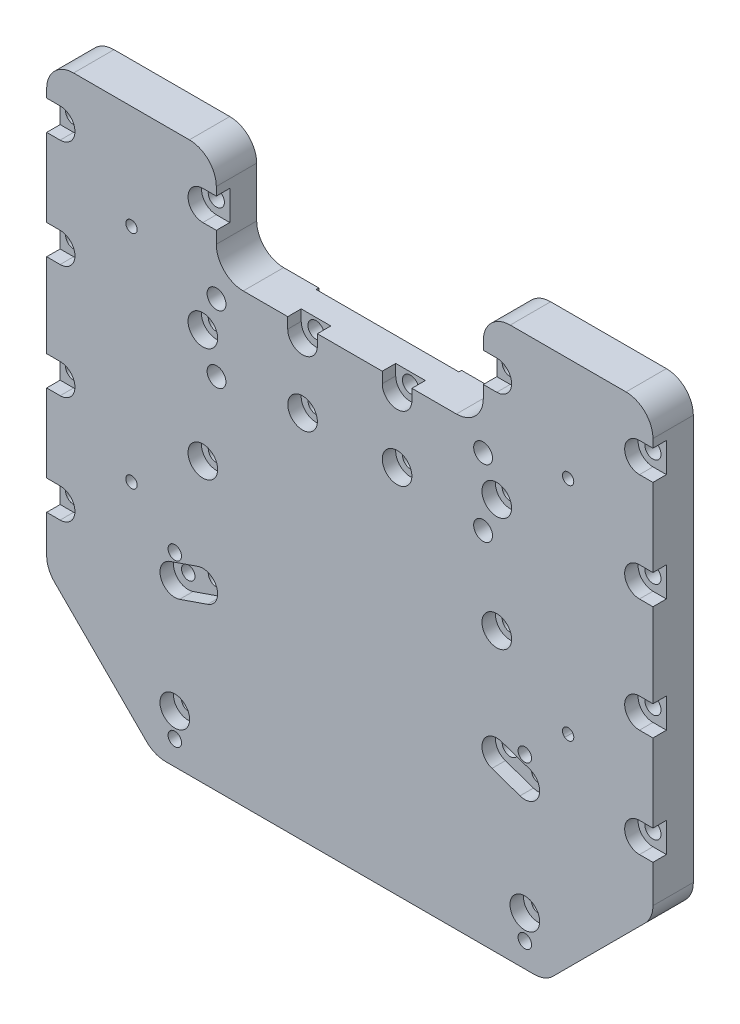
SolidWorks part; units mm, degrees
note: The reader was unsure of these and kept them because the rebuilt part matched: shared geometry of "Sketch16<3>", "Sketch16<4>".
ref_plane "Default Plane" through (193.6635, -121.6579, 15) normal (0, 0, -1) x (-1, 0, 0)
sketch3d "Bounding-Box_Cut-List-Item1"
  line L0 (225.1635, 160.2579, 0) -> (0, 160.2579, 0) construction
  line L1 (0, 160.2579, 0) -> (0, -44.1421, 0) construction
  line L2 (0, -44.1421, 0) -> (225.1635, -44.1421, 0) construction
  line L3 (225.1635, -44.1421, 0) -> (225.1635, 160.2579, 0) construction
  line L4 (225.1635, 160.2579, 15) -> (0, 160.2579, 15) construction
  line L5 (0, 160.2579, 15) -> (0, -44.1421, 15) construction
  line L6 (0, -44.1421, 15) -> (225.1635, -44.1421, 15) construction
  line L7 (225.1635, -44.1421, 15) -> (225.1635, 160.2579, 15) construction
  line L8 (225.1635, 160.2579, 0) -> (225.1635, 160.2579, 15) construction
  line L9 (0, 160.2579, 0) -> (0, 160.2579, 15) construction
  line L10 (0, -44.1421, 0) -> (0, -44.1421, 15) construction
  line L11 (225.1635, -44.1421, 0) -> (225.1635, -44.1421, 15) construction
material "6061 Alloy"
ref_plane "Front Plane" through (0, 0, 0) normal (0, 0, 1) x (1, 0, 0)
ref_plane "Top Plane" through (0, 0, 0) normal (0, 1, 0) x (1, 0, 0)
ref_plane "Right Plane" through (0, 0, 0) normal (1, 0, 0) x (0, 0, -1)
sketch "Sketch1" plane through (0, 0, 0) normal (0, 0, 1) x (1, 0, 0)
  line L0 (130.6635, -57.95) -> (130.6635, -106.45) construction
  line L1 (130.6635, -106.45) -> (131.6635, -107.45) construction
  line L2 (131.6635, -107.45) -> (140.6453, -107.45) construction
  line L3 (140.6453, -107.45) -> (140.6453, -120.8) construction
  line L4 (140.6453, -120.8) -> (183.6818, -120.8) construction
  line L5 (183.6818, -120.8) -> (183.6818, -107.45) construction
  line L6 (183.6818, -107.45) -> (192.6635, -107.45) construction
  line L7 (192.6635, -107.45) -> (193.6635, -106.45) construction
  line L8 (193.6635, -106.45) -> (193.6635, -57.95) construction
  line L9 (193.6635, -57.95) -> (192.6635, -56.95) construction
  line L10 (192.6635, -56.95) -> (183.6818, -56.95) construction
  line L11 (183.6818, -56.95) -> (183.6818, -43.6) construction
  line L12 (183.6818, -43.6) -> (140.6453, -43.6) construction
  line L13 (140.6453, -43.6) -> (140.6453, -56.95) construction
  line L14 (140.6453, -56.95) -> (131.6635, -56.95) construction
  line L15 (131.6635, -56.95) -> (130.6635, -57.95) construction
  line L16 (130.6635, 24.25) -> (130.6635, -24.25) construction
  line L17 (130.6635, -24.25) -> (131.6635, -25.25) construction
  line L18 (131.6635, -25.25) -> (140.6453, -25.25) construction
  line L19 (140.6453, -25.25) -> (140.6453, -38.6) construction
  line L20 (140.6453, -38.6) -> (183.6818, -38.6) construction
  line L21 (183.6818, -38.6) -> (183.6818, -25.25) construction
  line L22 (183.6818, -25.25) -> (192.6635, -25.25) construction
  line L23 (192.6635, -25.25) -> (193.6635, -24.25) construction
  line L24 (193.6635, -24.25) -> (193.6635, 24.25) construction
  line L25 (193.6635, 24.25) -> (192.6635, 25.25) construction
  line L26 (192.6635, 25.25) -> (183.6818, 25.25) construction
  line L27 (183.6818, 25.25) -> (183.6818, 38.6) construction
  line L28 (183.6818, 38.6) -> (140.6453, 38.6) construction
  line L29 (140.6453, 38.6) -> (140.6453, 25.25) construction
  line L30 (140.6453, 25.25) -> (131.6635, 25.25) construction
  line L31 (131.6635, 25.25) -> (130.6635, 24.25) construction
  line L32 (-31.5, -57.95) -> (-31.5, -106.45) construction
  line L33 (-31.5, -106.45) -> (-30.5, -107.45) construction
  line L34 (-30.5, -107.45) -> (-21.5182, -107.45) construction
  line L35 (-21.5182, -107.45) -> (-21.5182, -120.8) construction
  line L36 (-21.5182, -120.8) -> (21.5182, -120.8) construction
  line L37 (21.5182, -120.8) -> (21.5182, -107.45) construction
  line L38 (21.5182, -107.45) -> (30.5, -107.45) construction
  line L39 (30.5, -107.45) -> (31.5, -106.45) construction
  line L40 (31.5, -106.45) -> (31.5, -57.95) construction
  line L41 (31.5, -57.95) -> (30.5, -56.95) construction
  line L42 (30.5, -56.95) -> (21.5182, -56.95) construction
  line L43 (21.5182, -56.95) -> (21.5182, -43.6) construction
  line L44 (21.5182, -43.6) -> (-21.5182, -43.6) construction
  line L45 (-21.5182, -43.6) -> (-21.5182, -56.95) construction
  line L46 (-21.5182, -56.95) -> (-30.5, -56.95) construction
  line L47 (-30.5, -56.95) -> (-31.5, -57.95) construction
  line L48 (-31.5, 24.25) -> (-31.5, -24.25) construction
  line L49 (-31.5, -24.25) -> (-30.5, -25.25) construction
  line L50 (-30.5, -25.25) -> (-21.5182, -25.25) construction
  line L51 (-21.5182, -25.25) -> (-21.5182, -38.6) construction
  line L52 (-21.5182, -38.6) -> (21.5182, -38.6) construction
  line L53 (21.5182, -38.6) -> (21.5182, -25.25) construction
  line L54 (21.5182, -25.25) -> (30.5, -25.25) construction
  line L55 (30.5, -25.25) -> (31.5, -24.25) construction
  line L56 (31.5, -24.25) -> (31.5, 24.25) construction
  line L57 (31.5, 24.25) -> (30.5, 25.25) construction
  line L58 (30.5, 25.25) -> (21.5182, 25.25) construction
  line L59 (21.5182, 25.25) -> (21.5182, 38.6) construction
  line L60 (21.5182, 38.6) -> (-21.5182, 38.6) construction
  line L61 (-21.5182, 38.6) -> (-21.5182, 25.25) construction
  line L62 (-21.5182, 25.25) -> (-30.5, 25.25) construction
  line L63 (-30.5, 25.25) -> (-31.5, 24.25) construction
  line L64 (130.6635, -57.95) -> (130.6635, -106.45) construction
  line L65 (130.6635, -106.45) -> (131.6635, -107.45) construction
  line L66 (131.6635, -107.45) -> (140.6453, -107.45) construction
  line L67 (140.6453, -107.45) -> (140.6453, -120.8) construction
  line L68 (140.6453, -120.8) -> (183.6818, -120.8) construction
  line L69 (183.6818, -120.8) -> (183.6818, -107.45) construction
  line L70 (183.6818, -107.45) -> (192.6635, -107.45) construction
  line L71 (192.6635, -107.45) -> (193.6635, -106.45) construction
  line L72 (193.6635, -106.45) -> (193.6635, -57.95) construction
  line L73 (193.6635, -57.95) -> (192.6635, -56.95) construction
  line L74 (192.6635, -56.95) -> (183.6818, -56.95) construction
  line L75 (183.6818, -56.95) -> (183.6818, -43.6) construction
  line L76 (183.6818, -43.6) -> (140.6453, -43.6) construction
  line L77 (140.6453, -43.6) -> (140.6453, -56.95) construction
  line L78 (140.6453, -56.95) -> (131.6635, -56.95) construction
  line L79 (131.6635, -56.95) -> (130.6635, -57.95) construction
  line L80 (130.6635, 24.25) -> (130.6635, -24.25) construction
  line L81 (130.6635, -24.25) -> (131.6635, -25.25) construction
  line L82 (131.6635, -25.25) -> (140.6453, -25.25) construction
  line L83 (140.6453, -25.25) -> (140.6453, -38.6) construction
  line L84 (140.6453, -38.6) -> (183.6818, -38.6) construction
  line L85 (183.6818, -38.6) -> (183.6818, -25.25) construction
  line L86 (183.6818, -25.25) -> (192.6635, -25.25) construction
  line L87 (192.6635, -25.25) -> (193.6635, -24.25) construction
  line L88 (193.6635, -24.25) -> (193.6635, 24.25) construction
  line L89 (193.6635, 24.25) -> (192.6635, 25.25) construction
  line L90 (192.6635, 25.25) -> (183.6818, 25.25) construction
  line L91 (183.6818, 25.25) -> (183.6818, 38.6) construction
  line L92 (183.6818, 38.6) -> (140.6453, 38.6) construction
  line L93 (140.6453, 38.6) -> (140.6453, 25.25) construction
  line L94 (140.6453, 25.25) -> (131.6635, 25.25) construction
  line L95 (131.6635, 25.25) -> (130.6635, 24.25) construction
  line L96 (-31.5, -57.95) -> (-31.5, -106.45) construction
  line L97 (-31.5, -106.45) -> (-30.5, -107.45) construction
  line L98 (-30.5, -107.45) -> (-21.5182, -107.45) construction
  line L99 (-21.5182, -107.45) -> (-21.5182, -120.8) construction
  line L100 (-21.5182, -120.8) -> (21.5182, -120.8) construction
  line L101 (21.5182, -120.8) -> (21.5182, -107.45) construction
  line L102 (21.5182, -107.45) -> (30.5, -107.45) construction
  line L103 (30.5, -107.45) -> (31.5, -106.45) construction
  line L104 (31.5, -106.45) -> (31.5, -57.95) construction
  line L105 (31.5, -57.95) -> (30.5, -56.95) construction
  line L106 (30.5, -56.95) -> (21.5182, -56.95) construction
  line L107 (21.5182, -56.95) -> (21.5182, -43.6) construction
  line L108 (21.5182, -43.6) -> (-21.5182, -43.6) construction
  line L109 (-21.5182, -43.6) -> (-21.5182, -56.95) construction
  line L110 (-21.5182, -56.95) -> (-30.5, -56.95) construction
  line L111 (-30.5, -56.95) -> (-31.5, -57.95) construction
  line L112 (-31.5, 24.25) -> (-31.5, -24.25) construction
  line L113 (-31.5, -24.25) -> (-30.5, -25.25) construction
  line L114 (-30.5, -25.25) -> (-21.5182, -25.25) construction
  line L115 (-21.5182, -25.25) -> (-21.5182, -38.6) construction
  line L116 (-21.5182, -38.6) -> (21.5182, -38.6) construction
  line L117 (21.5182, -38.6) -> (21.5182, -25.25) construction
  line L118 (21.5182, -25.25) -> (30.5, -25.25) construction
  line L119 (30.5, -25.25) -> (31.5, -24.25) construction
  line L120 (31.5, -24.25) -> (31.5, 24.25) construction
  line L121 (31.5, 24.25) -> (30.5, 25.25) construction
  line L122 (30.5, 25.25) -> (21.5182, 25.25) construction
  line L123 (21.5182, 25.25) -> (21.5182, 38.6) construction
  line L124 (21.5182, 38.6) -> (-21.5182, 38.6) construction
  line L125 (-21.5182, 38.6) -> (-21.5182, 25.25) construction
  line L126 (-21.5182, 25.25) -> (-30.5, 25.25) construction
  line L127 (-30.5, 25.25) -> (-31.5, 24.25) construction
  line L129 (-31.5, 38.6) -> (193.6635, 38.6)
  line L130 (-31.5, 38.6) -> (-31.5, -165.8)
  line L131 (-31.5, -165.8) -> (193.6635, -165.8)
  line L132 (193.6635, 38.6) -> (193.6635, -165.8)
  circle A1 centre (188.6635, -102.2) radius 2.5
  circle A2 centre (188.6635, -102.2) radius 2.5 construction
  circle A3 centre (188.6635, -62.2) radius 2.5
  circle A4 centre (188.6635, -62.2) radius 2.5 construction
  circle A5 centre (135.6635, -62.2) radius 2.5
  circle A6 centre (135.6635, -62.2) radius 2.5 construction
  circle A7 centre (135.6635, -102.2) radius 2.5
  circle A8 centre (135.6635, -102.2) radius 2.5 construction
  circle A9 centre (188.6635, -20) radius 2.5
  circle A10 centre (188.6635, -20) radius 2.5 construction
  circle A11 centre (188.6635, 20) radius 2.5
  circle A12 centre (188.6635, 20) radius 2.5 construction
  circle A13 centre (135.6635, 20) radius 2.5
  circle A14 centre (135.6635, 20) radius 2.5 construction
  circle A15 centre (135.6635, -20) radius 2.5
  circle A16 centre (135.6635, -20) radius 2.5 construction
  circle A17 centre (26.5, -102.2) radius 2.5
  circle A18 centre (26.5, -102.2) radius 2.5 construction
  circle A19 centre (26.5, -62.2) radius 2.5
  circle A20 centre (26.5, -62.2) radius 2.5 construction
  circle A21 centre (-26.5, -62.2) radius 2.5
  circle A22 centre (-26.5, -62.2) radius 2.5 construction
  circle A23 centre (-26.5, -102.2) radius 2.5
  circle A24 centre (-26.5, -102.2) radius 2.5 construction
  circle A25 centre (26.5, -20) radius 2.5
  circle A26 centre (26.5, -20) radius 2.5 construction
  circle A27 centre (26.5, 20) radius 2.5
  circle A28 centre (26.5, 20) radius 2.5 construction
  circle A29 centre (-26.5, 20) radius 2.5
  circle A30 centre (-26.5, 20) radius 2.5 construction
  circle A31 centre (-26.5, -20) radius 2.5
  circle A32 centre (-26.5, -20) radius 2.5 construction
  circle A33 centre (63.5318, -28.2202) radius 2.15
  circle A34 centre (63.5318, -28.2202) radius 2.15
  circle A35 centre (98.6318, -28.2202) radius 2.15
  circle A36 centre (98.6318, -28.2202) radius 2.15
  circle A37 centre (98.6318, -4.0202) radius 2.15
  circle A38 centre (98.6318, -4.0202) radius 2.15
  circle A39 centre (63.5318, -4.0202) radius 2.15
  circle A40 centre (63.5318, -4.0202) radius 2.15
  dimension "D17" = 45
  dimension "D1" = 0
  dimension "D2" = 0
  dimension "D3" = 0
  dimension "D4" = 0
  dimension "D5" = 0
  dimension "D6" = 0
  dimension "D7" = 0
  dimension "D8" = 0
  dimension "D9" = 0
  dimension "D10" = 0
  dimension "D11" = 0
  dimension "D12" = 0
  dimension "D13" = 0
  dimension "D14" = 0
  dimension "D15" = 0
  dimension "D16" = 0
  dimension "D18" = 0
  dimension "D19" = 0
  dimension "D20" = 0
  dimension "D21" = 0
extrude "Boss-Extrude1" add sketch "Sketch1" along normal blind 15 contours L129 L132 L131 L130
sketch "holesLocations" plane through (0, 0, 15) normal (0, 0, 1) x (1, 0, 0)
  line L0 (135.6635, 20) -> (188.6635, -20) construction
  line L1 (135.6635, -62.2) -> (188.6635, -102.2) construction
  line L2 (-26.5, 20) -> (26.5, -20) construction
  line L3 (-26.5, -62.2) -> (26.5, -102.2) construction
  circle A0 centre (63.5318, -28.2202) radius 2.15 construction
  circle A1 centre (98.6318, -28.2202) radius 2.15 construction
  circle A2 centre (98.6318, -4.0202) radius 2.15 construction
  circle A3 centre (63.5318, -4.0202) radius 2.15 construction
  circle A4 centre (63.5318, -28.2202) radius 2.15
  circle A5 centre (98.6318, -28.2202) radius 2.15
  circle A6 centre (98.6318, -4.0202) radius 2.15
  circle A7 centre (63.5318, -4.0202) radius 2.15
  point P0 (135.6635, -20)
  point P2 (135.6635, 20)
  point P4 (188.6635, 20)
  point P6 (188.6635, -20)
  point P8 (188.6635, -62.2)
  point P10 (135.6635, -62.2)
  point P12 (188.6635, -102.2)
  point P14 (135.6635, -102.2)
  point P16 (-26.5, -102.2)
  point P18 (26.5, -62.2)
  point P20 (26.5, -102.2)
  point P22 (-26.5, -62.2)
  point P24 (-26.5, -20)
  point P26 (26.5, -20)
  point P28 (26.5, 20)
  point P30 (-26.5, 20)
  point P40 (0, 0)
  point P41 (0, -82.2)
  point P43 (162.1635, -82.2)
  point P44 (162.1635, 0)
hole_wizard "Hole1" positions "3DSketch1" profile "Sketch5" legacy end condition up to next
sketch3d "3DSketch1"
  point P0 (-26.5, 20, 15)
  point P3 (26.5, -20, 15)
  point P6 (26.5, 20, 15)
  point P9 (-26.5, -20, 15)
  point P12 (26.5, -62.2, 15)
  point P15 (26.5, -102.2, 15)
  point P18 (-26.5, -62.2, 15)
  point P21 (-26.5, -102.2, 15)
  point P24 (135.6635, 20, 15)
  point P27 (135.6635, -20, 15)
  point P30 (188.6635, 20, 15)
  point P33 (188.6635, -62.2, 15)
  point P36 (188.6635, -20, 15)
  point P39 (135.6635, -102.2, 15)
  point P42 (135.6635, -62.2, 15)
  point P45 (188.6635, -102.2, 15)
  point P48 (63.5318, -4.0202, 15)
  point P51 (63.5318, -28.2202, 15)
  point P54 (98.6318, -28.2202, 15)
  point P57 (98.6318, -4.0202, 15)
sketch "Sketch5" plane through (-26.5, 20, 15) normal (1, 0, 0) x (0, -1, 0)
  line L0 (0, 0) -> (0, 15)
  line L1 (0, 15) -> (3, 15)
  line L2 (3, 15) -> (3, 5)
  line L3 (3, 5) -> (5.5, 5)
  line L4 (5.5, 5) -> (5.5, 0)
  line L5 (5.5, 0) -> (0, 0)
  line L6 (0, 110) -> (0, -10) construction
  dimension "Diameter" = 6
  dimension "Depth" = 15
  dimension "C-Bore Diameter" = 11
  dimension "C-Bore Depth" = 5
hole_wizard "M5x0.8 Tapped Hole1" positions "3DSketch2" profile "Sketch7" tap size "M5x0.8" standard "ANSI Metric" end condition up to next
sketch3d "3DSketch2"
  line L0 (135.6635, -62.2, 15) -> (188.6635, -102.2, 15) construction
  line L1 (-26.5, 20, 15) -> (26.5, -20, 15) construction
  point P0 (0, 0, 0)
  point P3 (0, -82.2, 15)
  point P6 (162.1635, 0, 15)
  point P13 (162.1635, -82.2, 15)
  point P15 (162.1635, -82.2, 15)
  point P17 (162.1635, -82.2, 15)
  point P19 (0, 0, 15)
  point P30 (162.1635, -82.2, 15)
  point P32 (162.164, -82.2004, 15)
sketch "Sketch7" plane through (162.164, -82.2004, 15) normal (1, 0, 0) x (0, -1, 0)
  line L0 (0, 0) -> (0, 15.001)
  line L1 (0, 15.001) -> (2.1, 15.001)
  line L2 (2.1, 15.001) -> (2.1, 0)
  line L5 (2.1, 0) -> (0, 0)
  line L11 (0, -6.35) -> (0, 107.95) construction
  dimension "Thru Tap Drill Dia." = 4.2
  dimension "Thru Tap Drill Depth" = 15.001
cosmetic thread "Hole Thread9" parameters "D2"=5
cosmetic thread "Hole Thread11" parameters "D2"=5
cosmetic thread "Hole Thread14" parameters "D2"=5
cosmetic thread "Hole Thread15" parameters "D2"=5
cosmetic thread "Hole Thread16" parameters "D2"=5
cosmetic thread "Hole Thread17" parameters "D2"=5
sketch "Sketch9" plane through (0, 0, 15) normal (0, 0, 1) x (1, 0, 0)
  line L0 (-31.5, 38.6) -> (-31.5, 22.2913) construction
  line L1 (-26.5, 14.5) -> (-31.5, 14.5)
  line L2 (-26.5, 14.5) -> (-26.5, 25.5)
  line L3 (-26.5, 25.5) -> (-31.5, 25.5)
  line L4 (-31.5, 14.5) -> (-31.5, 25.5)
  line L5 (-31.5, 17.7087) -> (-31.5, -17.7087) construction
  line L6 (-26.5, -25.5) -> (-31.5, -25.5)
  line L7 (-26.5, -25.5) -> (-26.5, -14.5)
  line L8 (-26.5, -14.5) -> (-31.5, -14.5)
  line L9 (-31.5, -25.5) -> (-31.5, -14.5)
  line L10 (-31.5, -22.2913) -> (-31.5, -59.9087) construction
  line L11 (-26.5, -67.7) -> (-31.5, -67.7)
  line L12 (-26.5, -67.7) -> (-26.5, -56.7)
  line L13 (-26.5, -56.7) -> (-31.5, -56.7)
  line L14 (-31.5, -67.7) -> (-31.5, -56.7)
  line L15 (-31.5, -64.4913) -> (-31.5, -99.9087) construction
  line L16 (-26.5, -107.7) -> (-31.5, -107.7)
  line L17 (-26.5, -107.7) -> (-26.5, -96.7)
  line L18 (-26.5, -96.7) -> (-31.5, -96.7)
  line L19 (-31.5, -107.7) -> (-31.5, -96.7)
  line L20 (193.6635, 17.7087) -> (193.6635, -17.7087) construction
  line L21 (188.6635, 25.5) -> (193.6635, 25.5)
  line L22 (188.6635, 25.5) -> (188.6635, 14.5)
  line L23 (188.6635, 14.5) -> (193.6635, 14.5)
  line L24 (193.6635, 25.5) -> (193.6635, 14.5)
  line L25 (193.6635, -22.2913) -> (193.6635, -59.9087) construction
  line L26 (188.6635, -14.5) -> (193.6635, -14.5)
  line L27 (188.6635, -14.5) -> (188.6635, -25.5)
  line L28 (188.6635, -25.5) -> (193.6635, -25.5)
  line L29 (193.6635, -14.5) -> (193.6635, -25.5)
  line L30 (193.6635, -64.4913) -> (193.6635, -99.9087) construction
  line L31 (188.6635, -56.7) -> (193.6635, -56.7)
  line L32 (188.6635, -56.7) -> (188.6635, -67.7)
  line L33 (188.6635, -67.7) -> (193.6635, -67.7)
  line L34 (193.6635, -56.7) -> (193.6635, -67.7)
  line L35 (193.6635, -104.4913) -> (193.6635, -165.8) construction
  line L36 (188.6635, -96.7) -> (193.6635, -96.7)
  line L37 (188.6635, -96.7) -> (188.6635, -107.7)
  line L38 (188.6635, -107.7) -> (193.6635, -107.7)
  line L39 (193.6635, -96.7) -> (193.6635, -107.7)
  arc A0 (-31.5, 17.7087) -> (-31.5, 22.2913) centre (-26.5, 20) ccw construction
  arc A1 (-31.5, -22.2913) -> (-31.5, -17.7087) centre (-26.5, -20) ccw construction
  arc A2 (-31.5, -64.4913) -> (-31.5, -59.9087) centre (-26.5, -62.2) ccw construction
  arc A3 (-31.5, -104.4913) -> (-31.5, -99.9087) centre (-26.5, -102.2) ccw construction
  arc A4 (193.6635, 22.2913) -> (193.6635, 17.7087) centre (188.6635, 20) ccw construction
  arc A5 (193.6635, -17.7087) -> (193.6635, -22.2913) centre (188.6635, -20) ccw construction
  arc A6 (193.6635, -59.9087) -> (193.6635, -64.4913) centre (188.6635, -62.2) ccw construction
  arc A7 (193.6635, -99.9087) -> (193.6635, -104.4913) centre (188.6635, -102.2) ccw construction
  arc M23 (-31.5, 22.2913) -> (-31.5, 17.7087) centre (-26.5, 20) cw
  line M24 (-31.5, 17.7087) -> (-31.5, -17.7087)
  arc M25 (-31.5, -17.7087) -> (-31.5, -22.2913) centre (-26.5, -20) cw
  line M26 (-31.5, -22.2913) -> (-31.5, -59.9087)
  arc M27 (-31.5, -59.9087) -> (-31.5, -64.4913) centre (-26.5, -62.2) cw
  line M28 (-31.5, -64.4913) -> (-31.5, -99.9087)
  arc M29 (-31.5, -99.9087) -> (-31.5, -104.4913) centre (-26.5, -102.2) cw
  line M30 (-31.5, -104.4913) -> (-31.5, -165.8)
  line M32 (193.6635, -165.8) -> (193.6635, -104.4913)
  arc M33 (193.6635, -104.4913) -> (193.6635, -99.9087) centre (188.6635, -102.2) cw
  line M34 (193.6635, -99.9087) -> (193.6635, -64.4913)
  arc M35 (193.6635, -64.4913) -> (193.6635, -59.9087) centre (188.6635, -62.2) cw
  line M36 (193.6635, -59.9087) -> (193.6635, -22.2913)
  arc M37 (193.6635, -22.2913) -> (193.6635, -17.7087) centre (188.6635, -20) cw
  line M38 (193.6635, -17.7087) -> (193.6635, 17.7087)
  arc M39 (193.6635, 17.7087) -> (193.6635, 22.2913) centre (188.6635, 20) cw
  line M40 (193.6635, 22.2913) -> (193.6635, 38.6)
  line M42 (-31.5, 38.6) -> (-31.5, 22.2913)
extrude "Cut-Extrude1" cut sketch "Sketch9" against normal up to surface (5 mm away) contours L1 M23 M24 | L3 M23 M42 | L8 M25 M24 | L6 M25 M26 | L13 M27 M26 | L11 M27 M28 | L18 M29 M28 | L16 M29 M30 | L38 M33 M32 | L36 M33 M34 | L33 M35 M34 | L31 M35 M36 | L28 M37 M36 | L26 M37 M38 | L23 M39 M38 | L21 M39 M40 up to face at (-23.5, 20, 10)
sketch "Sketch10" plane through (0, 0, 15) normal (0, 0, 1) x (1, 0, 0)
  line L0 (-31.5, -165.8) -> (193.6635, -165.8) construction
  line L1 (16.0818, -156.8) -> (146.0818, -156.8)
  line L2 (16.0818, -156.8) -> (16.0818, -96.8)
  line L3 (16.0818, -96.8) -> (146.0818, -96.8)
  line L4 (146.0818, -156.8) -> (146.0818, -96.8)
  line L5 (16.0818, -147.8) -> (146.0818, -147.8)
  line L6 (16.0818, -147.8) -> (16.0818, -105.8)
  line L7 (16.0818, -105.8) -> (146.0818, -105.8)
  line L8 (146.0818, -147.8) -> (146.0818, -105.8)
  line L9 (81.0818, -156.8) -> (81.0818, -165.8)
  dimension "D1" = 130
  dimension "D2" = 60
  dimension "D3" = 42
  dimension "D4" = 9
  dimension "D5" = 18
hole_wizard "M6x1.0 Tapped Hole1" positions "3DSketch3" profile "Sketch12" tap size "M6x1.0" standard "ANSI Metric" end condition up to next
sketch3d "3DSketch3"
  point P0 (16.0818, -96.8, 15)
  point P3 (146.0818, -96.8, 15)
  point P6 (146.0818, -156.8, 15)
  point P9 (16.0818, -156.8, 15)
sketch "Sketch12" plane through (16.0818, -96.8, 15) normal (1, 0, 0) x (0, -1, 0)
  line L0 (0, 0) -> (0, 15)
  line L1 (0, 15) -> (2.5, 15)
  line L2 (2.5, 15) -> (2.5, 0)
  line L5 (2.5, 0) -> (0, 0)
  line L11 (0, -6.35) -> (0, 107.95) construction
  dimension "Thru Tap Drill Dia." = 5
  dimension "Thru Tap Drill Depth" = 15
cosmetic thread "Hole Thread5" parameters "D2"=6
cosmetic thread "Hole Thread6" parameters "D2"=6
cosmetic thread "Hole Thread7" parameters "D2"=6
cosmetic thread "Hole Thread8" parameters "D2"=6
hole_wizard "Hole2" positions "3DSketch4" profile "Sketch14" legacy end condition up to next
sketch3d "3DSketch4"
  point P0 (16.0818, -105.8, 15)
  point P3 (16.0818, -147.8, 15)
  point P6 (146.0818, -105.8, 15)
  point P9 (146.0818, -147.8, 15)
sketch "Sketch14" plane through (16.0818, -105.8, 15) normal (1, 0, 0) x (0, -1, 0)
  line L0 (0, 0) -> (0, 15)
  line L1 (0, 15) -> (2.5, 15)
  line L2 (2.5, 15) -> (2.5, 5)
  line L3 (2.5, 5) -> (5.5, 5)
  line L4 (5.5, 5) -> (5.5, 0)
  line L5 (5.5, 0) -> (0, 0)
  line L6 (0, 110) -> (0, -10) construction
  dimension "Diameter" = 5
  dimension "Depth" = 15
  dimension "C-Bore Diameter" = 11
  dimension "C-Bore Depth" = 5
sketch "Sketch15" plane through (0, 0, 15) normal (0, 0, 1) x (1, 0, 0)
  line L0 (14.2855, -100.6016) -> (24.7037, -97.0016)
  line L1 (17.8781, -110.9984) -> (28.2963, -107.3984)
  line L2 (81.0818, 38.6) -> (81.0818, -165.8) construction
  line L3 (-31.5, 38.6) -> (193.6635, 38.6) construction
  line L4 (-31.5, -165.8) -> (193.6635, -165.8) construction
  line L5 (144.2855, -110.9984) -> (133.8672, -107.3984)
  line L6 (147.8781, -100.6016) -> (137.4598, -97.0016)
  circle A0 centre (26.5, -102.2) radius 5.5 construction
  circle A1 centre (16.0818, -105.8) radius 5.5 construction
  circle A2 centre (26.5, -102.2) radius 5.5 construction
  circle A3 centre (26.5, -102.2) radius 5.5
  circle A4 centre (16.0818, -105.8) radius 5.5
  circle A5 centre (146.0818, -105.8) radius 5.5
  circle A6 centre (135.6635, -102.2) radius 5.5
extrude "Cut-Extrude2" cut sketch "Sketch15" against normal up to surface (5 mm away) contours A4 L1 A3 L0 | L6 A6 L5 A5 up to face at (138.6635, -102.2, 10)
chamfer "Chamfer1" distance 40 angle 45 2 edges at (193.6635, -165.8, 7.5) (-31.5, -165.8, 7.5)
sketch "Sketch16" plane through (0, 0, 0) normal (0, 0, -1) x (-1, 0, 0)
  line L0 (-73.2681, 13.4798) -> (-66.2681, 13.4798) construction
  line L1 (-73.2681, 13.4798) -> (-66.2681, 13.4798)
  line L2 (-105.5818, 1.3798) -> (-105.5818, -33.6202) construction
  line L3 (-105.5818, -33.6202) -> (-56.5818, -33.6202) construction
  line L4 (-56.5818, -33.6202) -> (-56.5818, 1.3798) construction
  line L5 (-56.5818, 1.3798) -> (-105.5818, 1.3798) construction
  line L6 (-95.7787, 1.8798) -> (-66.3848, 1.8798) construction
  line L7 (-66.3848, 1.8798) -> (-66.3848, 9.8798) construction
  line L8 (-66.3848, 9.8798) -> (-95.7787, 9.8798) construction
  line L9 (-95.7787, 9.8798) -> (-95.7787, 1.8798) construction
  line L10 (-75.0818, 9.8798) -> (-87.0818, 9.8798) construction
  line L11 (-105.5818, 1.3798) -> (-105.5818, -33.6202)
  line L12 (-105.5818, -33.6202) -> (-56.5818, -33.6202)
  line L13 (-56.5818, -33.6202) -> (-56.5818, 1.3798)
  line L14 (-56.5818, 1.3798) -> (-105.5818, 1.3798)
  line L15 (-95.7787, 1.8798) -> (-66.3848, 1.8798)
  line L16 (-66.3848, 1.8798) -> (-66.3848, 9.8798)
  line L17 (-66.3848, 9.8798) -> (-95.7787, 9.8798)
  line L18 (-95.7787, 9.8798) -> (-95.7787, 1.8798)
  line L19 (-75.0818, 9.8798) -> (-87.0818, 9.8798)
  line L20 (31.5, 38.6) -> (-193.6635, 38.6) construction
  line L21 (-107.5818, -35.6202) -> (-54.5818, -35.6202)
  line L22 (-107.5818, -35.6202) -> (-107.5818, 38.6)
  line L23 (-107.5818, 38.6) -> (-54.5818, 38.6)
  line L24 (-54.5818, -35.6202) -> (-54.5818, 38.6)
  line L25 (-8.5, -165.8) -> (-153.6635, -165.8) construction
  line L26 (-107.5818, 38.6) -> (-54.5818, 38.6)
  line L27 (-107.5818, 38.6) -> (-107.5818, 1.4899)
  line L28 (-107.5818, 1.4899) -> (-54.5818, 1.4899)
  line L29 (-54.5818, 38.6) -> (-54.5818, 1.4899)
  line L30 (-107.5818, -35.6202) -> (-54.5818, -35.6202)
  line L31 (-107.5818, -35.6202) -> (-107.5818, -165.8)
  line L32 (-107.5818, -165.8) -> (-54.5818, -165.8)
  line L33 (-54.5818, -35.6202) -> (-54.5818, -165.8)
  line L34 (-130.6635, 24.25) -> (-130.6635, -24.25) construction
  line L35 (-130.6635, 0) -> (-31.5, 0)
  line L36 (-130.6635, 0) -> (-130.6635, 38.6)
  line L37 (-130.6635, 38.6) -> (-31.5, 38.6)
  line L38 (-31.5, 0) -> (-31.5, 38.6)
  line L39 (-31.5, -24.25) -> (-31.5, 24.25) construction
  line L40 (-130.6635, 24.25) -> (-130.6635, -24.25)
  line L41 (-31.5, -24.25) -> (-31.5, 24.25)
  line M42 (-153.6635, -165.8) -> (-8.5, -165.8)
  dimension "D1" = 2
  dimension "D2" = 2
  dimension "D3" = 2
extrude "Cut-Extrude3" cut sketch "Sketch16" against normal blind 1
extrude "Cut-Extrude4" cut sketch "Sketch16<3>" against normal offset from surface (5 mm away) 2 contours L33 L21 L31 M42 offset beyond the face yes
sketch "Sketch16<3>" plane through (0, 0, 0) normal (0, 0, -1) x (-1, 0, 0) same geometry as "Sketch16"
extrude "Cut-Extrude5" cut sketch "Sketch16<4>" against normal through all
sketch "Sketch16<4>" plane through (0, 0, 0) normal (0, 0, -1) x (-1, 0, 0) same geometry as "Sketch16"
sketch "Sketch17" plane through (0, 0, 15) normal (0, 0, 1) x (1, 0, 0)
  line L0 (26.5, 20) -> (37.5353, 20) construction
  line L1 (26.5, 25.5) -> (37.5353, 25.5)
  line L2 (26.5, 14.5) -> (37.5353, 14.5)
  line L3 (63.5318, -4.0202) -> (63.5318, 6.879) construction
  line L4 (58.0318, -4.0202) -> (58.0318, 6.879)
  line L5 (69.0318, -4.0202) -> (69.0318, 6.879)
  line L6 (98.6318, -4.0202) -> (98.6318, 8.2381) construction
  line L7 (93.1318, -4.0202) -> (93.1318, 8.2381)
  line L8 (104.1318, -4.0202) -> (104.1318, 8.2381)
  line L9 (135.6635, 20) -> (124.6727, 20) construction
  line L10 (135.6635, 14.5) -> (124.6727, 14.5)
  line L11 (135.6635, 25.5) -> (124.6727, 25.5)
  arc A0 (26.5, 25.5) -> (26.5, 14.5) centre (26.5, 20) ccw
  arc A1 (37.5353, 14.5) -> (37.5353, 25.5) centre (37.5353, 20) ccw
  arc A2 (58.0318, -4.0202) -> (69.0318, -4.0202) centre (63.5318, -4.0202) ccw
  arc A3 (69.0318, 6.879) -> (58.0318, 6.879) centre (63.5318, 6.879) ccw
  arc A4 (93.1318, -4.0202) -> (104.1318, -4.0202) centre (98.6318, -4.0202) ccw
  arc A5 (104.1318, 8.2381) -> (93.1318, 8.2381) centre (98.6318, 8.2381) ccw
  arc A6 (135.6635, 14.5) -> (135.6635, 25.5) centre (135.6635, 20) ccw
  arc A7 (124.6727, 25.5) -> (124.6727, 14.5) centre (124.6727, 20) ccw
  arc A8 (31.5, 22.2913) -> (31.5, 17.7087) centre (26.5, 20) ccw construction
  arc A9 (59.7783, 0) -> (67.2852, 0) centre (63.5318, -4.0202) ccw construction
  arc A10 (94.8783, 0) -> (102.3852, 0) centre (98.6318, -4.0202) ccw construction
  arc A11 (130.6635, 17.7087) -> (130.6635, 22.2913) centre (135.6635, 20) ccw construction
  point P3 (32.0176, 20)
  point P8 (63.5318, 1.4294)
  point P16 (98.6318, 2.109)
  point P24 (130.1681, 20)
extrude "Cut-Extrude6" cut sketch "Sketch17" against normal up to surface (5 mm away) up to face at (66.5318, -4.0202, 10)
fillet "Fillet1" radius 10 10 edges at (-31.5, -125.8, 7.5) (8.5, -165.8, 7.5) (153.6635, -165.8, 7.5) (193.6635, -125.8, 7.5) (193.6635, 38.6, 7.5) (130.6635, 38.6, 7.5) (130.6635, 0, 7.5) (31.5, 0, 7.5) (-31.5, 38.6, 7.5) (31.5, 38.6, 7.5)
sketch "Sketch18" plane through (0, 0, 15) normal (0, 0, 1) x (1, 0, 0)
  line L0 (26.5, -20) -> (31.5818, -20) construction
  line L1 (81.0818, 0) -> (81.0818, -63.4482) construction
  line L2 (31.5818, -7.5) -> (130.5818, -7.5) construction
  line L3 (31.5818, -7.5) -> (31.5818, -32.5) construction
  line L4 (31.5818, -32.5) -> (130.5818, -32.5) construction
  line L5 (130.5818, -7.5) -> (130.5818, -32.5) construction
  line L7 (69.0318, 0) -> (93.1318, 0) construction
  point P8 (81.0818, -7.5)
  point P15 (31.5818, -20)
  dimension "D1" = 99
  dimension "D2" = 25
hole_wizard "oldSpindleMountM8holes" positions "3DSketch5" profile "Sketch19" tap size "M8x1.0" standard "ANSI Metric" end condition through all
sketch3d "3DSketch5"
  point P0 (31.5818, -7.5, 15)
  point P3 (31.5818, -32.5, 15)
  point P6 (130.5818, -7.5, 15)
  point P9 (130.5818, -32.5, 15)
sketch "Sketch19" plane through (31.5818, -7.5, 15) normal (1, 0, 0) x (0, -1, 0)
  line L0 (0, 0) -> (0, 15.005)
  line L1 (0, 15.005) -> (3.5, 15.005)
  line L2 (3.5, 15.005) -> (3.5, 0)
  line L5 (3.5, 0) -> (0, 0)
  line L11 (0, -6.35) -> (0, 107.95) construction
  dimension "Thru Tap Drill Dia." = 7
  dimension "Thru Tap Drill Depth" = 15.005
cosmetic thread "Hole Thread1" parameters "D2"=8
cosmetic thread "Hole Thread2" parameters "D2"=8
cosmetic thread "Hole Thread3" parameters "D2"=8
cosmetic thread "Hole Thread4" parameters "D2"=8
